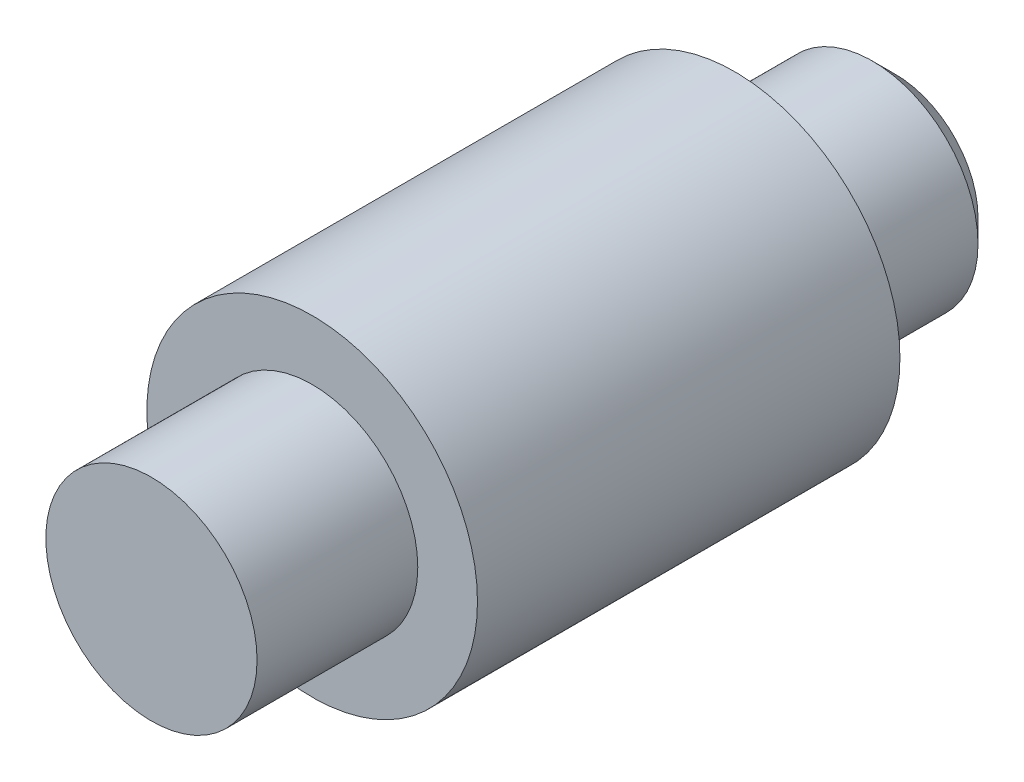
SolidWorks part; units mm, degrees
ref_plane "Front Plane" through (0, 0, 0) normal (0, 0, 1) x (1, 0, 0)
ref_plane "Top Plane" through (0, 0, 0) normal (0, 1, 0) x (1, 0, 0)
ref_plane "Right Plane" through (0, 0, 0) normal (1, 0, 0) x (0, 0, -1)
sketch "Sketch2" plane through (0, 0, 0) normal (0, 0, 1) x (1, 0, 0)
  circle A0 centre (0, 0) radius 1.25
  dimension "D1" = 2.5
sketch "Sketch3" plane through (0, 0, 0) normal (0, 0, 1) x (1, 0, 0)
  line L5 (-3.6, 3.6) -> (3.6, 3.6) construction
  line L6 (-3.6, 3.6) -> (-3.6, -3.6) construction
  line L7 (-3.6, -3.6) -> (3.6, -3.6) construction
  line L8 (3.6, 3.6) -> (3.6, -3.6) construction
  circle A0 centre (0, 0) radius 3.6
  point P4 (0, 3.6)
  point P6 (-3.6, 0)
  dimension "D1" = 7.2
extrude "Boss-Extrude1" add sketch "Sketch3" along normal blind 9.2
sketch "Sketch4" plane through (0, 0, 0) normal (0, 0, 1) x (1, 0, 0)
  circle A0 centre (0, 0) radius 2.3
  dimension "D1" = 4.6
extrude "Boss-Extrude2" add sketch "Sketch4" against normal blind 3.5
sketch "Sketch5" plane through (0, 0, 9.2) normal (0, 0, 1) x (1, 0, 0)
  circle A0 centre (0, 0) radius 2.3
  dimension "D1" = 4.6
extrude "Boss-Extrude3" add sketch "Sketch5" along normal blind 3.5
chamfer "Chamfer1" distance 0.5 angle 45 1 edges at (2.3, 0, -3.5)
equation "\"length\"=9.2"
equation "\"D1@Boss-Extrude1\"=\"length\""
equation "\"hole\"=4.6"
equation "\"D1@Sketch5\"=\"hole\""
equation "\"D1@Sketch4\"=\"hole\""
equation "\"foot\"=3.5"
equation "\"D1@Boss-Extrude3\"=\"foot\""
equation "\"D1@Boss-Extrude2\"=\"foot\""
